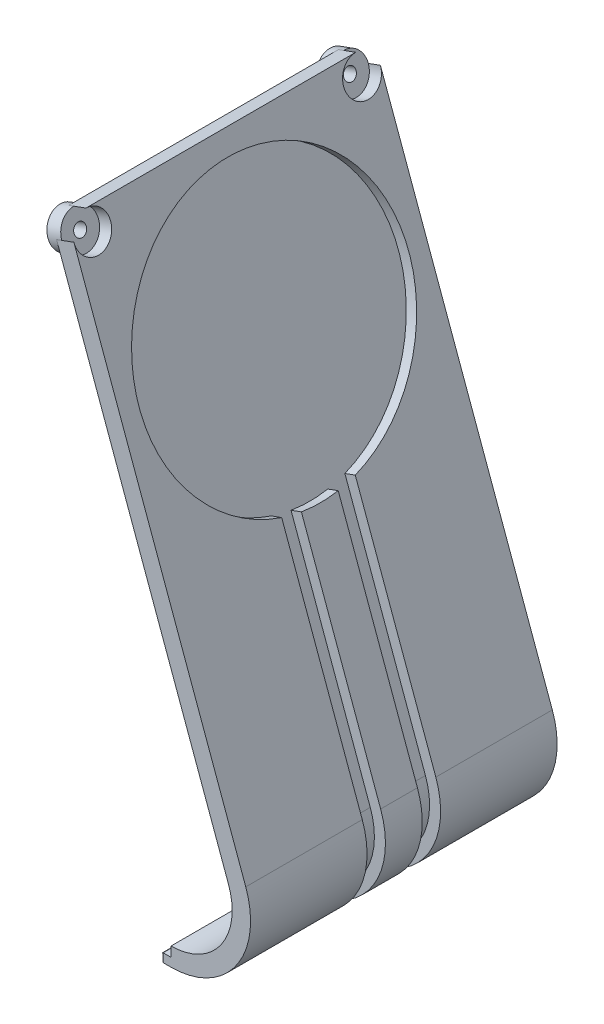
SolidWorks part; units mm, degrees
material "PLA"
ref_plane "前视基准面" through (0, 0, 0) normal (0, 0, 1) x (1, 0, 0)
ref_plane "上视基准面" through (0, 0, 0) normal (0, 1, 0) x (1, 0, 0)
ref_plane "右视基准面" through (0, 0, 0) normal (1, 0, 0) x (0, 0, -1)
other "Configuration Table"
sketch "草图2" plane through (0, 0, 0) normal (0, 0, 1) x (1, 0, 0)
  line L0 (40.5059, 20.4699) -> (9.8204, 104.7777) construction
  line L5 (40.5059, 20.4699) -> (11.4415, 100.3236)
  line L7 (31.0341, 7.0497) -> (31.0341, 5.5751) construction
  line L8 (10.418, 106.0594) -> (12.7673, 106.9145) construction
  arc A0 (31.1341, 7.0497) -> (40.5059, 20.4699) centre (31.109, 17.0497) ccw
  arc A1 (31.109, 7.0497) -> (40.5059, 20.4699) centre (31.109, 17.0497) ccw construction
  dimension "D3" = 0.1
  dimension "D2" = 10
  dimension "D1" = 5.74
extrude "整体拉伸-薄壁1" add sketch "草图2" along normal mid plane 50 thin thin type one direction wall 3
sketch "草图4" plane through (45.1656, 16.4389, 0) normal (0.9397, 0.342, 0) x (0, 0, -1)
  line L0 (-25, 90.3601) -> (25, 90.3601) construction
  circle A0 centre (0, 64.9601) radius 22
  dimension "D1" = 44
  dimension "D2" = 25.4
extrude "中间圆切除-拉伸1" cut sketch "草图4" against normal blind 1.8
sketch "草图3" plane through (0, 0, 0) normal (0, 0, 1) x (1, 0, 0)
  line L0 (43.325, 21.4959) -> (14.2606, 101.3496) construction
  line L1 (43.325, 21.4959) -> (14.2606, 101.3496) construction
  line L2 (31.1417, 4.0497) -> (31.1341, 7.0497) construction
  line L5 (41.6335, 20.8803) -> (28.7809, 56.1926)
  line L6 (41.6335, 20.8803) -> (12.5692, 100.734) construction
  line L7 (31.1371, 5.8497) -> (31.1371, 5.8497) construction
  line L9 (28.7809, 56.1926) -> (30.4724, 56.8082) construction
  line L16 (28.7809, 56.1926) -> (27.7549, 59.0116)
  line L17 (29.3399, 5.9493) -> (20.0387, 10.2344) construction
  arc A0 (31.1341, 7.0497) -> (40.5059, 20.4699) centre (31.109, 17.0497) ccw construction
  arc A1 (20.0387, 10.2344) -> (43.325, 21.4959) centre (31.109, 17.0497) ccw construction
  arc A2 (31.1371, 5.8497) -> (41.6335, 20.8803) centre (31.109, 17.0497) ccw
  dimension "D2" = 3
  dimension "D1" = 1.8
extrude "线槽切除-拉伸-薄壁1" cut sketch "草图3" against normal blind 3 from offset 6 thin thin type one direction wall 1.8
mirror "镜向1" about plane through (0, 0, 0) normal (0, 0, 1) of "线槽切除-拉伸-薄壁1"
sketch "草图7" plane through (42.3465, 15.4129, 0) normal (-0.9397, -0.342, 0) x (0, 0, 1)
  line L0 (25, 90.3601) -> (-25, 90.3601) construction
  line L1 (-25, 5.3816) -> (-25, 90.3601) construction
  line L3 (0, 90.3601) -> (0, 71.6076) construction
  circle A0 centre (-22, 87.3601) radius 1
  circle A1 centre (-22, 87.3601) radius 3
  circle A2 centre (22, 87.3601) radius 3
  circle A3 centre (22, 87.3601) radius 1
  dimension "D1" = 2
extrude "螺丝柱凸台-拉伸2" add sketch "草图7" along normal blind 1.5
sketch "草图8" plane through (42.3465, 15.4129, 0) normal (-0.9397, -0.342, 0) x (0, 0, 1)
  line L0 (0, 90.3601) -> (0, 70.5485) construction
  line L1 (-26, 91.3601) -> (-22, 91.3601)
  line L2 (-26, 91.3601) -> (-26, 87.3601)
  line L3 (-26, 87.3601) -> (-25, 87.3601)
  line L4 (-22, 91.3601) -> (-22, 90.3601)
  line L5 (22, 90.3601) -> (-22, 90.3601) construction
  line L6 (22, 91.3601) -> (22, 90.3601)
  line L7 (26, 87.3601) -> (25, 87.3601)
  line L8 (26, 91.3601) -> (26, 87.3601)
  line L9 (26, 91.3601) -> (22, 91.3601)
  line L10 (-25, 5.3816) -> (-25, 87.3601) construction
  arc A0 (-25, 87.3601) -> (-22, 90.3601) centre (-22, 87.3601) ccw
  arc A2 (25, 87.3601) -> (22, 90.3601) centre (22, 87.3601) cw
  dimension "D2" = 4
  dimension "D3" = 4
  dimension "D4" = 1
  dimension "D5" = 1
extrude "螺丝柱切除-拉伸1" cut sketch "草图8" along normal blind 2.1 from surface starting at face at (30.929, 55.5537, 0)
sketch "草图9" plane through (42.3465, 15.4129, 0) normal (-0.9397, -0.342, 0) x (0, 0, 1)
  line L0 (-22, 90.3601) -> (-25, 90.3601) construction
  line L1 (-22, 90.3601) -> (-25, 90.3601)
  line L2 (-25, 87.3601) -> (-25, 90.3601) construction
  line L3 (-25, 87.3601) -> (-25, 90.3601)
  line L4 (0, 90.3601) -> (0, 58.5215) construction
  line L5 (22, 90.3601) -> (-22, 90.3601) construction
  line L6 (25, 87.3601) -> (25, 90.3601)
  line L7 (22, 90.3601) -> (25, 90.3601)
  circle A0 centre (-22, 87.3601) radius 3 construction
  arc A1 (-22, 90.3601) -> (-25, 87.3601) centre (-22, 87.3601) ccw
  arc A2 (22, 90.3601) -> (25, 87.3601) centre (22, 87.3601) cw
extrude "螺丝使圆切除-拉伸2" cut sketch "草图9" against normal up to next
sketch "草图10" plane through (42.3465, 15.4129, 0) normal (-0.9397, -0.342, 0) x (0, 0, 1)
  circle A0 centre (22, 87.3601) radius 1 construction
  circle A1 centre (22, 87.3601) radius 1
  circle A2 centre (-22, 87.3601) radius 1 construction
  circle A3 centre (-22, 87.3601) radius 1
extrude "螺丝孔切除-拉伸3" cut sketch "草图10" against normal mid plane 5
sketch "草图11" plane through (31.1516, 0.0783, 0) normal (-1, -0.0025, 0) x (0, 0, 1)
  line L0 (-25, 3.9714) -> (-25, 6.9714) construction
  line L1 (-25, 5.3714) -> (-6.1, 5.3714)
  line L2 (-25, 5.3714) -> (-25, 3.9714)
  line L3 (-25, 3.9714) -> (-6.1, 3.9714)
  line L4 (-6.1, 5.3714) -> (-6.1, 3.9714)
  line L5 (25, 3.9714) -> (6, 3.9714) construction
  line L6 (6.1, 5.3714) -> (25, 5.3714)
  line L7 (6.1, 5.3714) -> (6.1, 3.9714)
  line L8 (6.1, 3.9714) -> (25, 3.9714)
  line L9 (25, 5.3714) -> (25, 3.9714)
  line L11 (-6, 3.9714) -> (-6, 5.7714) construction
  line L13 (6, 3.9714) -> (6, 5.7714) construction
  line L14 (25, 6.9714) -> (-25, 6.9714) construction
  dimension "D1" = 1.6
  dimension "D2" = 0.1
  dimension "D3" = 0.1
  dimension "D4" = 1.6
extrude "底部卡扣凸台-拉伸3" add sketch "草图11" along normal blind 1.5
fillet "底部卡扣圆角1" radius 0.25 8 edges at (29.6381, 5.446, 15.55) (29.6399, 4.746, 25) (29.6417, 4.046, 15.55) (29.6399, 4.746, 6.1) (29.6381, 5.446, -15.55) (29.6399, 4.746, -6.1) (29.6417, 4.046, -15.55) (29.6399, 4.746, -25)
